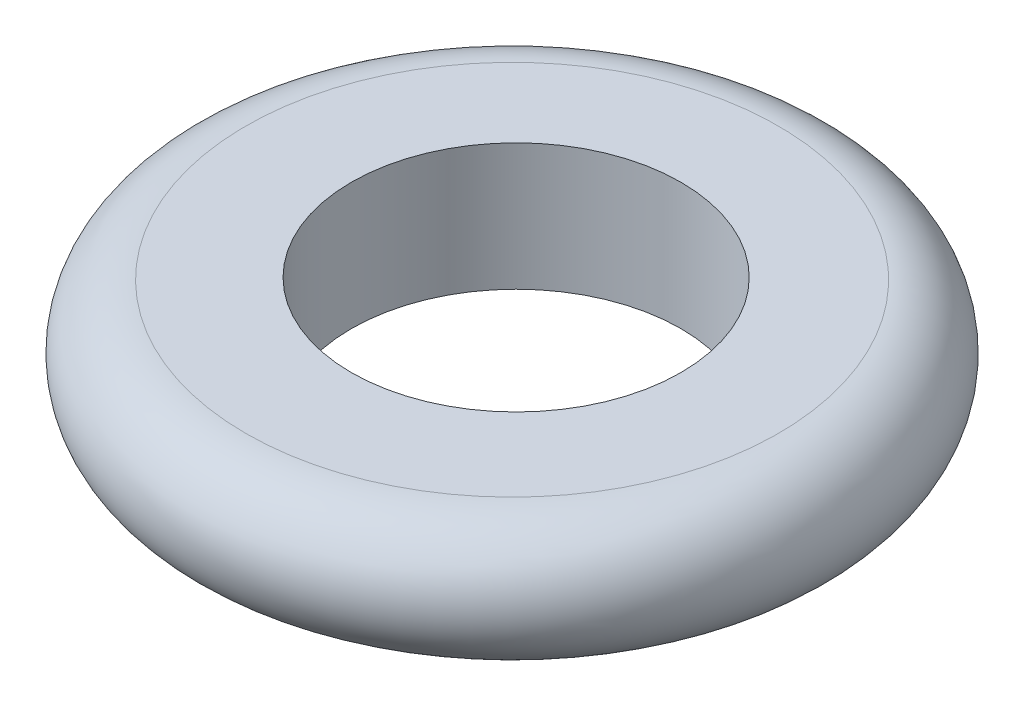
SolidWorks part; units mm, degrees
ref_plane "Plan de face" through (0, 0, 0) normal (0, 0, 1) x (1, 0, 0)
ref_plane "Plan de dessus" through (0, 0, 0) normal (0, 1, 0) x (1, 0, 0)
ref_plane "Plan de droite" through (0, 0, 0) normal (1, 0, 0) x (0, 0, -1)
sketch "Esquisse1" plane through (0, 0, 0) normal (0, 1, 0) x (1, 0, 0)
  circle A0 centre (0, 0) radius 13
  circle A1 centre (0, 0.1593) radius 6.5
  point P5 (0, 0)
extrude "Boss.-Extru.1" add sketch "Esquisse1" along normal blind 5
fillet "Congé4" 2 edges at (0, 5, 13) (0, 0, 13) type full round first side face at (0, 5, 13) second side face at (0, 0, 13) middle face at (0, 5, 13)
